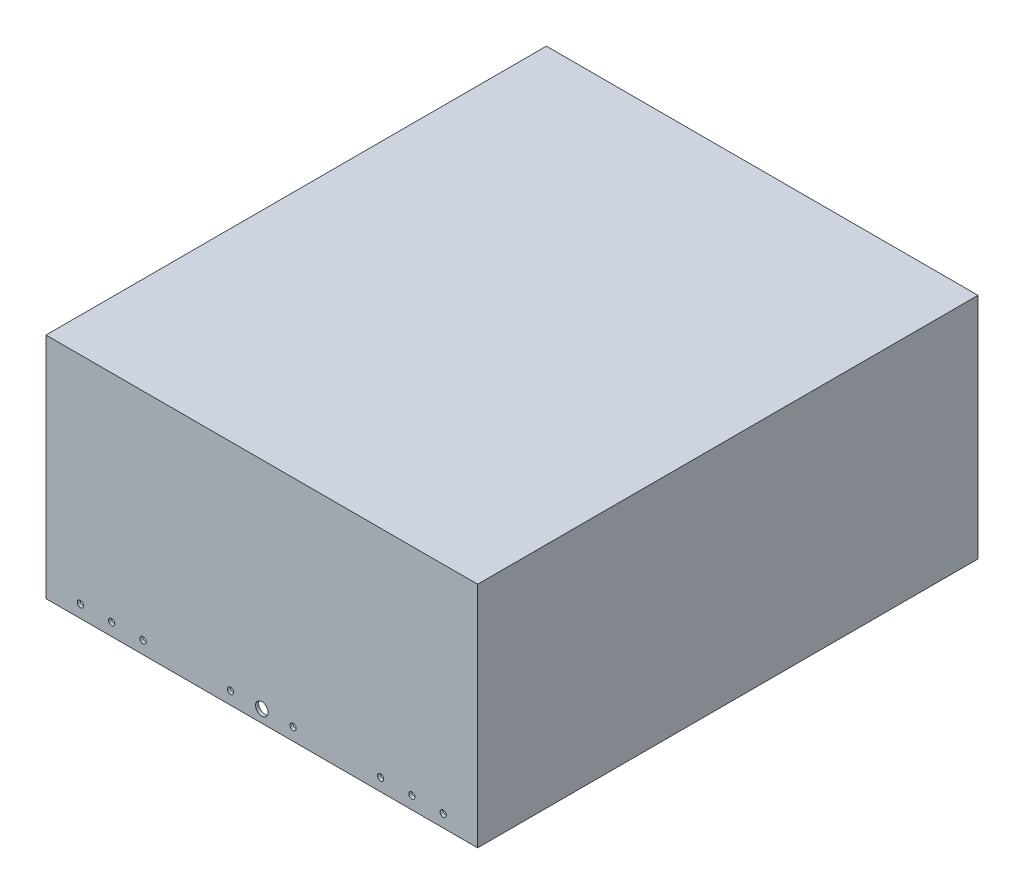
SolidWorks part; units mm, degrees
ref_plane "Front Plane" through (0, 0, 0) normal (0, 0, 1) x (1, 0, 0)
ref_plane "Top Plane" through (0, 0, 0) normal (0, 1, 0) x (1, 0, 0)
ref_plane "Right Plane" through (0, 0, 0) normal (1, 0, 0) x (0, 0, -1)
sketch "Sketch1" plane through (0, 0, 0) normal (0, 0, 1) x (1, 0, 0)
  line L0 (0, 0) -> (3.175, 0)
  line L1 (3.175, 0) -> (3.175, 101.6)
  line L2 (3.175, 101.6) -> (434.975, 101.6)
  line L3 (434.975, 101.6) -> (434.975, -127)
  line L4 (434.975, -127) -> (438.15, -127)
  line L5 (438.15, -127) -> (438.15, 104.775)
  line L6 (438.15, 104.775) -> (0, 104.775)
  line L7 (0, 104.775) -> (0, 0)
  line L8 (3.175, 101.6) -> (3.175, 104.775) construction
  dimension "D1" = 3.175
  dimension "D2" = 431.8
  dimension "D3" = 101.6
  dimension "D4" = 228.6
extrude "Boss-Extrude1" add sketch "Sketch1" along normal blind 508
sketch "Sketch2" plane through (0, 0, 0) normal (-1, 0, 0) x (0, 0, 1)
  line L0 (508, 0) -> (0, 0) construction
  line L1 (139.7, -76.2) -> (165.1, -76.2)
  line L2 (508, 101.6) -> (508, -127) construction
  line L3 (508, -76.2) -> (508, 0)
  line L4 (63.5, 0) -> (508, 0)
  line L5 (0, 104.775) -> (0, 0) construction
  line L6 (165.1, -76.2) -> (165.1, -127)
  line L7 (508, -127) -> (0, -127) construction
  line L8 (165.1, -127) -> (508, -127)
  line L9 (508, -127) -> (508, -76.2)
  arc A0 (63.5, 0) -> (139.7, -76.2) centre (63.5, -76.2) cw
  dimension "D1" = 76.2
  dimension "D2" = 63.5
  dimension "D3" = 25.4
extrude "Boss-Extrude2" add sketch "Sketch2" against normal up to surface (3.175 mm away) up to face at (3.175, 50.8, 254)
sketch "Sketch3" plane through (0, 0, 508) normal (0, 0, 1) x (1, 0, 0)
  line L1 (0, 104.775) -> (438.15, 104.775)
  line L2 (0, 104.775) -> (0, -127)
  line L3 (0, -127) -> (438.15, -127)
  line L4 (438.15, 104.775) -> (438.15, -127)
extrude "Boss-Extrude3" add sketch "Sketch3" against normal blind 3.175
sketch "Sketch4" plane through (0, 0, 508) normal (0, 0, 1) x (1, 0, 0)
  line L0 (219.075, 104.775) -> (219.075, -127) construction
  line L1 (438.15, 104.775) -> (0, 104.775) construction
  line L2 (0, -127) -> (438.15, -127) construction
  circle A0 centre (34.925, -114.3) radius 3.175
  circle A1 centre (98.425, -114.3) radius 3.175
  circle A2 centre (66.675, -114.3) radius 3.175
  circle A3 centre (339.725, -114.3) radius 3.175
  circle A4 centre (371.475, -114.3) radius 3.175
  circle A5 centre (403.225, -114.3) radius 3.175
  circle A6 centre (187.325, -114.3) radius 3.175
  circle A7 centre (250.825, -114.3) radius 3.175
  circle A8 centre (219.075, -114.3) radius 6.35
  point P22 (0, 0)
  dimension "D3" = 6.35
  dimension "D7" = 12.7
  dimension "D1" = 63.5
  dimension "D2" = 12.7
  dimension "D4" = 31.75
  dimension "D5" = 152.4
  dimension "D6" = 63.5
extrude "Cut-Extrude1" cut sketch "Sketch4" against normal up to surface (3.175 mm away) up to face at (219.075, -12.7, 504.825)
equation "\"D4@Sketch4\"=\"D1@Sketch4\"/2"
